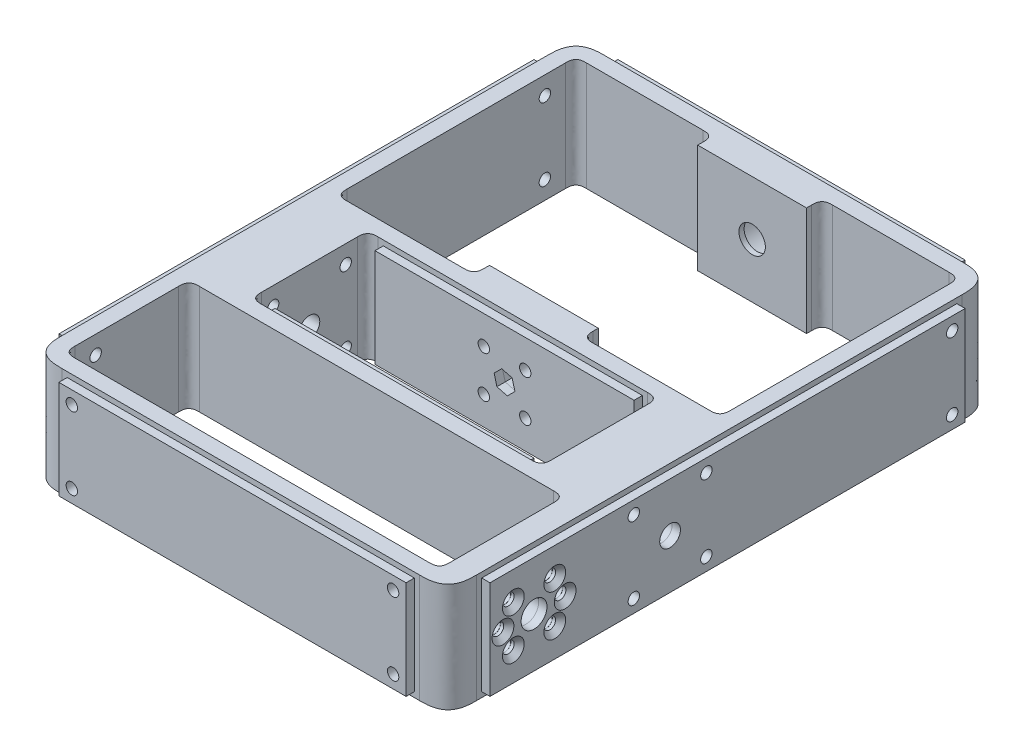
SolidWorks part; units mm, degrees
ref_plane "Front Plane" through (0, 0, 0) normal (0, 0, 1) x (1, 0, 0)
ref_plane "Top Plane" through (0, 0, 0) normal (0, 1, 0) x (1, 0, 0)
ref_plane "Right Plane" through (0, 0, 0) normal (1, 0, 0) x (0, 0, -1)
sketch "Sketch1" plane through (0, 0, 0) normal (0, 1, 0) x (1, 0, 0)
  line L0 (-93.2979, 0) -> (107.2162, 0) construction
  line L1 (-93.2979, -52.5) -> (97.3404, -52.5) construction
  line L2 (-74, -76.5) -> (74, -76.5)
  line L3 (-80, 126.87) -> (80, 126.87)
  line L4 (-80, 126.87) -> (-80, -82.5)
  line L5 (-80, -82.5) -> (80, -82.5)
  line L6 (80, 126.87) -> (80, -82.5)
  line L7 (74, -76.5) -> (74, -28.5)
  line L8 (74, -28.5) -> (-74, -28.5)
  line L9 (-74, -28.5) -> (-74, -76.5)
  line L10 (-74, 120.87) -> (-74, 28.5)
  line L11 (-56, 22.5) -> (56, 22.5)
  line L12 (-56, 22.5) -> (-56, -22.5)
  line L13 (-56, -22.5) -> (56, -22.5)
  line L14 (56, 22.5) -> (56, -22.5)
  line L15 (-74, 28.5) -> (-21, 28.5)
  line L16 (-21, 28.5) -> (-21, 34.5)
  line L17 (-21, 34.5) -> (21, 34.5)
  line L18 (21, 34.5) -> (21, 28.5)
  line L19 (21, 28.5) -> (74, 28.5)
  line L20 (74, 28.5) -> (74, 120.87)
  line L22 (-74, 120.87) -> (-21, 120.87)
  line L23 (-21, 120.87) -> (-21, 114.87)
  line L24 (-21, 114.87) -> (21, 114.87)
  line L25 (21, 114.87) -> (21, 120.87)
  line L26 (21, 120.87) -> (74, 120.87)
  line L27 (-106.876, 46.5) -> (121.9857, 46.5) construction
  point P9 (0, -82.5)
  point P29 (0, -22.5)
  point P31 (0, 114.87)
  point P37 (-56, 0)
  dimension "D1" = 52.5
  dimension "D3" = 160
  dimension "D2" = 6
  dimension "D5" = 6
  dimension "D6" = 24
  dimension "D7" = 24
  dimension "D8" = 6
  dimension "D9" = 24
  dimension "D10" = 6
  dimension "D11" = 6
  dimension "D12" = 6
  dimension "D13" = 42
  dimension "D14" = 12
  dimension "D4" = 12
  dimension "D15" = 68.37
  dimension "D16" = 46.5
extrude "Boss-Extrude2" add sketch "Sketch1" along normal mid plane 42
fillet "Fillet2" radius 11 4 edges at (80, 0, -126.87) (-80, 0, 82.5) (-80, 0, -126.87) (80, 0, 82.5) curvature continuous yes
sketch "Sketch11" plane through (0, 0, 0) normal (0, 1, 0) x (1, 0, 0)
  line L8 (74, -28.5) -> (-74, -28.5) construction
  line L9 (70.7, -28.5) -> (80, -28.5)
  line L10 (83.2, 35.9489) -> (83.2, -108.345) construction
  line L11 (80, -71.5) -> (80, 115.87) construction
  line L12 (70.7, -28.5) -> (70.7, -76.5)
  line L13 (70.7, -76.5) -> (79.5287, -76.5)
  line L14 (80, -28.5) -> (80, -71.5)
  line L15 (-74, -76.5) -> (74, -76.5) construction
  line L16 (79.5287, -76.5) -> (80, -76.5) construction
  line L17 (80, -71.5) -> (80, -76.5) construction
  spline S0 degree 2 poles (-928.7412, -15.3439) (41.6602, -84.362) (71.2832, -82.4484) (72.514, -82.3689) (73.5428, -82.1401) (76.0869, -81.5744) (77.5752, -80.092) (79.066, -78.6071) (79.6366, -76.0586) (79.8669, -75.03) (79.9474, -73.7973) (81.8879, -44.1188) (12.1756, 926.183) knots -4.508241 -4.508241 -4.508241 0.125 0.125 0.25 0.25 0.5 0.5 0.75 0.75 0.875 0.875 5.490692 5.490692 5.490692 only from (69, -82.5) to (80, -71.5) construction
  spline S1 degree 2 poles (79.5287, -76.5) (79.5862, -76.2834) (79.6366, -76.0586) (79.8669, -75.03) (79.9474, -73.7973) (80, -72.9936) (80, -71.5) knots 0.727944 0.727944 0.727944 0.75 0.75 0.875 0.875 1 1 1
  spline S2 degree 2 poles (69, -82.5) (70.484, -82.5) (71.2832, -82.4484) (72.514, -82.3689) (73.5428, -82.1401) (76.0869, -81.5744) (77.5752, -80.092) (78.9345, -78.7381) (79.5287, -76.5) knots 0 0 0 0.125 0.125 0.25 0.25 0.5 0.5 0.727944 0.727944 0.727944 construction
  dimension "D1" = 3.2
  dimension "D2" = 12.5
extrude "Boss-Extrude5" add sketch "Sketch11" along normal mid plane 42
sketch "Sketch5" plane through (80, 0, 0) normal (1, 0, 0) x (0, 0, -1)
  line L8 (113.87, 19) -> (-69.5, 19)
  line L9 (-69.5, 19) -> (-69.5, -19)
  line L10 (-69.5, -19) -> (113.87, -19)
  line L11 (113.87, -19) -> (113.87, 19)
  line L12 (113.87, 19) -> (-69.5, 19)
  line L14 (-69.5, -19) -> (113.87, -19)
  line L15 (113.87, -19) -> (113.87, 19)
  line L19 (-69.5, 19) -> (-69.5, -19)
  dimension "D1" = 2
extrude "Boss-Extrude3" add sketch "Sketch5" along normal blind 3.2 separate body
sketch "Sketch9" plane through (-80, 0, 0) normal (-1, 0, 0) x (0, 0, 1)
  line L8 (-113.87, -19) -> (69.5, -19)
  line L9 (69.5, -19) -> (69.5, 19)
  line L10 (69.5, 19) -> (-113.87, 19)
  line L11 (-113.87, 19) -> (-113.87, -19)
  line L12 (-113.87, -19) -> (69.5, -19)
  line L13 (69.5, -19) -> (69.5, 19)
  line L14 (69.5, 19) -> (-113.87, 19)
  line L15 (-113.87, 19) -> (-113.87, -19)
  dimension "D1" = 2
extrude "Boss-Extrude4" add sketch "Sketch9" along normal blind 3.2 separate body
sketch "Sketch8" plane through (83.2, 0, 0) normal (1, 0, 0) x (0, 0, -1)
  line L1 (-14, 14) -> (14, 14) construction
  line L2 (-14, 14) -> (-14, -14) construction
  line L3 (-14, -14) -> (14, -14) construction
  line L4 (14, 14) -> (14, -14) construction
  line L5 (-14, 14) -> (14, -14) construction
  line L6 (-14, -14) -> (14, 14) construction
  line L16 (108.87, -14) -> (108.87, 14)
  line L17 (108.87, 14) -> (-64.5, 14)
  line L18 (-64.5, 14) -> (-64.5, -14)
  line L19 (-64.5, -14) -> (108.87, -14)
  line L20 (108.87, -14) -> (108.87, 14) construction
  line L21 (108.87, 14) -> (-64.5, 14) construction
  line L22 (-64.5, 14) -> (-64.5, -14) construction
  line L23 (-64.5, -14) -> (108.87, -14) construction
  circle A0 centre (0, 0) radius 4
  circle A1 centre (-14, 14) radius 2.2
  circle A2 centre (14, 14) radius 2.2
  circle A3 centre (14, -14) radius 2.2
  circle A4 centre (-14, -14) radius 2.2
  circle A9 centre (108.87, -14) radius 2.2
  circle A10 centre (108.87, 14) radius 2.2
  dimension "D1" = 8
  dimension "D2" = 4.4
  dimension "D4" = 5
extrude "Cut-Extrude5" cut sketch "Sketch8" against normal through all
sketch "Sketch6" plane through (0, 0, 0) normal (1, 0, 0) x (0, 0, -1)
  line L0 (-64.5, 0) -> (-40.5, 0) construction
  line L1 (-60.5, 8) -> (-44.5, 8) construction
  line L2 (-60.5, 8) -> (-60.5, -8) construction
  line L3 (-60.5, -8) -> (-44.5, -8) construction
  line L4 (-44.5, 8) -> (-44.5, -8) construction
  line L5 (-60.5, 8) -> (-44.5, -8) construction
  line L6 (-60.5, -8) -> (-44.5, 8) construction
  circle A0 centre (-52.5, 0) radius 5
  circle A1 centre (-60.5, 8) radius 2.2
  circle A2 centre (-44.5, 8) radius 2.2
  circle A3 centre (-44.5, -8) radius 2.2
  circle A4 centre (-60.5, -8) radius 2.2
  circle A5 centre (-64.5, 0) radius 2.2
  circle A6 centre (-40.5, 0) radius 2.2
  dimension "D1" = 52.5
  dimension "D4" = 4.4
  dimension "D5" = 10
  dimension "D2" = 16
  dimension "D3" = 24
extrude "Cut-Extrude3" cut sketch "Sketch6" along normal through all
sketch "Sketch17" plane through (-83.2, 0, 0) normal (-1, 0, 0) x (0, 0, 1)
  line L8 (-108.87, 14) -> (-108.87, -14)
  line L9 (-108.87, -14) -> (64.5, -14)
  line L10 (64.5, -14) -> (64.5, 14)
  line L11 (64.5, 14) -> (-108.87, 14)
  line L12 (-108.87, 14) -> (-108.87, -14) construction
  line L13 (-108.87, -14) -> (64.5, -14) construction
  line L14 (64.5, -14) -> (64.5, 14) construction
  line L15 (64.5, 14) -> (-108.87, 14) construction
  circle A0 centre (64.5, 14) radius 2.2
  circle A1 centre (64.5, -14) radius 2.2
  dimension "D2" = 4.4
extrude "Cut-Extrude11" cut sketch "Sketch17" against normal up to surface (9.2 mm away) up to face at (-74, 0, 52.5)
fillet "Fillet4" radius 4 16 edges at (70.7, 0, 28.5) (70.7, 0, 76.5) (-56, 0, -22.5) (-56, 0, 22.5) (56, 0, 22.5) (56, 0, -22.5) (74, 0, -28.5) (-74, 0, -28.5) (-74, 0, 28.5) (74, 0, -120.87) (-74, 0, -120.87) (-74, 0, 76.5) (21, 0, -120.87) (-21, 0, -120.87) (-21, 0, -28.5) (21, 0, -28.5) curvature continuous yes
sketch "Sketch18" plane through (83.2, 0, 0) normal (1, 0, 0) x (0, 0, -1)
  circle A0 centre (-60.5, -8) radius 2.2 construction
  circle A1 centre (-64.5, 0) radius 2.2 construction
  circle A2 centre (-60.5, 8) radius 2.2 construction
  circle A3 centre (-44.5, 8) radius 2.2 construction
  circle A4 centre (-40.5, 0) radius 2.2 construction
  circle A5 centre (-44.5, -8) radius 2.2 construction
  circle A6 centre (-60.5, -8) radius 2.2
  circle A7 centre (-64.5, 0) radius 2.2
  circle A8 centre (-60.5, 8) radius 2.2
  circle A9 centre (-44.5, 8) radius 2.2
  circle A10 centre (-40.5, 0) radius 2.2
  circle A11 centre (-44.5, -8) radius 2.2
  point P0 (-60.5, -8)
  point P2 (-64.5, 0)
  point P4 (-60.5, 8)
  point P6 (-44.5, 8)
  point P8 (-40.5, 0)
  point P10 (-44.5, -8)
hole_wizard "CSK for M4 Countersunk Flat Head Screw1" positions "Sketch18" profile "Sketch21" countersink size "M4" standard "DIN"
sketch "Sketch21" plane through (83.2, -8, 60.5) normal (0, 1, 0) x (0, 0, -1)
  line L0 (0, 0) -> (0, 13.8519)
  line L1 (0, 13.8519) -> (2.25, 12.5)
  line L2 (2.25, 12.5) -> (2.25, 1.95)
  line L3 (2.25, 1.95) -> (4.2, 0)
  line L5 (4.2, 0) -> (0, 0)
  line L6 (-2.25, 1.95) -> (-4.2, 0) construction
  line L10 (0, 13.8519) -> (-2.25, 12.5) construction
  line L11 (0, -6.35) -> (0, 107.95) construction
  dimension "Hole Dia." = 4.5
  dimension "Hole Depth" = 12.5
  dimension "Near C'Sink Dia." = 8.4
  dimension "Near C'Sink Angle" = 90
  dimension "Drill Angle" = 118
sketch "Sketch22" plane through (0, 0, -22.5) normal (0, 0, 1) x (1, 0, 0)
  line L8 (50, 19) -> (-50, 19)
  line L9 (-50, 19) -> (-50, -19)
  line L10 (-50, -19) -> (50, -19)
  line L11 (50, -19) -> (50, 19)
  line L12 (50, 19) -> (-50, 19)
  line L13 (-50, 19) -> (-50, -19)
  line L15 (50, -19) -> (50, 19)
  line L17 (-50, -19) -> (50, -19)
  dimension "D1" = 2
extrude "Boss-Extrude6" add sketch "Sketch22" along normal blind 3.2 separate body
sketch "Sketch29" plane through (0, 0, 22.5) normal (0, 0, -1) x (-1, 0, 0)
  line L8 (-50, -19) -> (50, -19)
  line L9 (50, -19) -> (50, 19)
  line L10 (50, 19) -> (-50, 19)
  line L11 (-50, 19) -> (-50, -19)
  line L12 (-50, -19) -> (50, -19)
  line L13 (50, -19) -> (50, 19)
  line L14 (50, 19) -> (-50, 19)
  line L15 (-50, 19) -> (-50, -19)
  dimension "D1" = 2
extrude "Boss-Extrude9" add sketch "Sketch29" along normal blind 3.2 separate body
sketch "Sketch23" plane through (0, 0, -126.87) normal (0, 0, -1) x (-1, 0, 0)
  line L8 (67, 19) -> (-67, 19)
  line L9 (-67, 19) -> (-67, -19)
  line L10 (-67, -19) -> (67, -19)
  line L11 (67, -19) -> (67, 19)
  line L12 (67, 19) -> (-67, 19)
  line L13 (-67, 19) -> (-67, -19)
  line L14 (-67, -19) -> (67, -19)
  line L15 (67, -19) -> (67, 19)
  dimension "D1" = 2
extrude "Boss-Extrude7" add sketch "Sketch23" along normal blind 3.2 separate body
sketch "Sketch24" plane through (0, 0, 0) normal (0, 0, 1) x (1, 0, 0)
  line L0 (2.9394, 2.9394) -> (-2.9394, -2.9394) construction
  line L1 (1.0759, -4.0153) -> (4.0153, -1.0759)
  line L2 (4.0153, -1.0759) -> (2.9394, 2.9394)
  line L3 (2.9394, 2.9394) -> (-1.0759, 4.0153)
  line L4 (-1.0759, 4.0153) -> (-4.0153, 1.0759)
  line L5 (-4.0153, 1.0759) -> (-2.9394, -2.9394)
  line L6 (-2.9394, -2.9394) -> (1.0759, -4.0153)
  line L7 (-8, -8) -> (8, -8) construction
  line L8 (-8, -8) -> (-8, 8) construction
  line L9 (-8, 8) -> (8, 8) construction
  line L10 (8, -8) -> (8, 8) construction
  line L11 (-8, -8) -> (8, 8) construction
  line L12 (-8, 8) -> (8, -8) construction
  circle A0 centre (0, 0) radius 3.6 construction
  circle A1 centre (-8, 8) radius 2.2
  circle A2 centre (8, 8) radius 2.2
  circle A3 centre (8, -8) radius 2.2
  circle A4 centre (-8, -8) radius 2.2
  dimension "D3" = 4.4
  dimension "D1" = 7.2
  dimension "D2" = 16
extrude "Cut-Extrude12" cut sketch "Sketch24" against normal up to surface (34.5 mm away) up to face at (0, 0, -34.5)
sketch "Sketch27" plane through (0, 0, 82.5) normal (0, 0, 1) x (1, 0, 0)
  line L8 (-67, -19) -> (67, -19)
  line L9 (67, -19) -> (67, 19)
  line L10 (67, 19) -> (-67, 19)
  line L11 (-67, 19) -> (-67, -19)
  line L12 (-67, -19) -> (67, -19)
  line L13 (67, -19) -> (67, 19)
  line L14 (67, 19) -> (-67, 19)
  line L15 (-67, 19) -> (-67, -19)
  dimension "D1" = 2
extrude "Boss-Extrude8" add sketch "Sketch27" along normal blind 3.2 separate body
sketch "Sketch28" plane through (0, 0, 85.7) normal (0, 0, 1) x (1, 0, 0)
  line L8 (-62, 14) -> (-62, -14)
  line L9 (-62, -14) -> (62, -14)
  line L10 (62, -14) -> (62, 14)
  line L11 (62, 14) -> (-62, 14)
  line L12 (-62, 14) -> (-62, -14) construction
  line L13 (-62, -14) -> (62, -14) construction
  line L14 (62, -14) -> (62, 14) construction
  line L15 (62, 14) -> (-62, 14) construction
  circle A0 centre (-62, 14) radius 2.2
  circle A1 centre (-62, -14) radius 2.2
  circle A2 centre (62, -14) radius 2.2
  circle A3 centre (62, 14) radius 2.2
  dimension "D2" = 4.4
extrude "Cut-Extrude14" cut sketch "Sketch28" against normal up to surface (9.2 mm away) up to face at (-35.825, 0, 76.5)
sketch "Sketch31" plane through (0, 0, 0) normal (1, 0, 0) x (0, 0, -1)
  line L1 (126.87, 21) -> (126.87, -21)
  line L2 (126.87, 21) -> (126.87, -21) construction
  line L5 (114.87, 21) -> (114.87, -21)
  line L6 (114.87, 21) -> (114.87, -21) construction
  line L8 (0, 0) -> (175.1797, 0) construction
  line L10 (116.87, 10.5) -> (126.87, 10.5)
  line L11 (126.87, 10.5) -> (126.87, 0)
  line L12 (126.87, 0) -> (114.87, 0)
  line L13 (116.87, 10.5) -> (116.87, 5.1)
  line L14 (116.87, 5.1) -> (114.87, 5.1)
  line L15 (114.87, 5.1) -> (114.87, 0)
  point P17 (0, 0)
  dimension "D1" = 10.2
  dimension "D2" = 21
revolve "Cut-Revolve1" cut sketch "Sketch31" angle 360 about L8
equation "\"motor_center_distance_to_axle\"= 52.5mm"
equation "\"width\"= 160mm"
equation "\"height\"= 42mm"
equation "\"wall_thickness\"= 6mm"
equation "\"aluminum_thickness\"= 3.2mm"
equation "\"D1@Sketch1\"=\"motor_center_distance_to_axle\""
equation "\"D3@Sketch1\"=\"width\""
equation "\"depth\"= 200mm"
equation "\"D2@Sketch1\"=\"wall_thickness\""
equation "\"D5@Sketch1\"=\"wall_thickness\""
equation "\"D8@Sketch1\"=\"wall_thickness\""
equation "\"D10@Sketch1\"=\"wall_thickness\""
equation "\"D11@Sketch1\"=\"wall_thickness\""
equation "\"D12@Sketch1\"=\"wall_thickness\""
equation "\"D13@Sketch1\"=\"height\""
equation "\"spine_width\"= 58.45mm"
equation "\"D1@Boss-Extrude2\"=\"height\""
equation "\"D1@Boss-Extrude3\"=\"aluminum_thickness\""
equation "\"D1@Sketch6\"=\"motor_center_distance_to_axle\""
equation "\"plate_hole_inset\"= 5mm"
equation "\"D1@Boss-Extrude4\"=\"aluminum_thickness\""
equation "\"D4@Sketch8\"=\"plate_hole_inset\""
equation "\"D1@Boss-Extrude5\"=\"height\""
equation "\"D1@Sketch11\"=\"aluminum_thickness\""
equation "\"D1@Sketch17\"=\"plate_hole_inset\""
equation "\"D1@Boss-Extrude7\"=\"aluminum_thickness\""
equation "\"D1@Boss-Extrude8\"=\"aluminum_thickness\""
equation "\"D1@Sketch28\"=\"plate_hole_inset\""
equation "\"D1@Boss-Extrude6\"=\"aluminum_thickness\""
equation "\"D1@Boss-Extrude9\"=\"aluminum_thickness\""
equation "\"D15@Sketch1\"=\"spine_width\"+(4.96mm*2)"
equation "\"spine_cavity_depth\"= 80mm"
equation "\"fillet_radius\"= 10mm"
